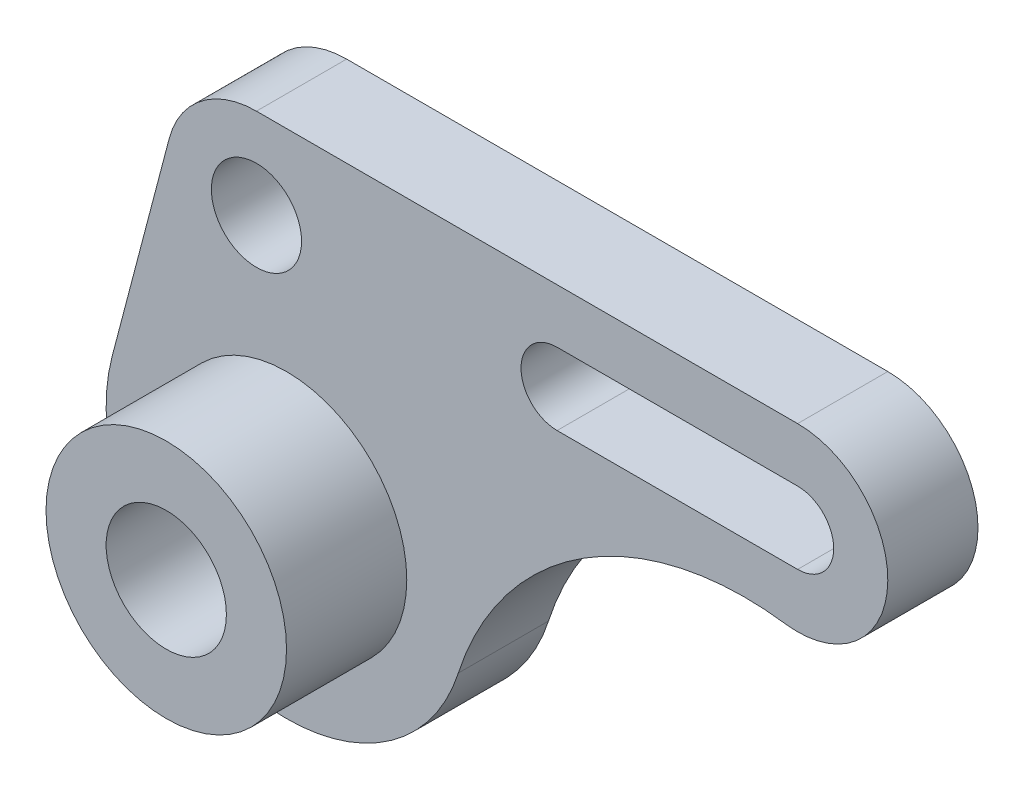
SolidWorks part; units mm, degrees
ref_plane "Front Plane" through (0, 0, 0) normal (0, 0, 1) x (1, 0, 0)
ref_plane "Top Plane" through (0, 0, 0) normal (0, 1, 0) x (1, 0, 0)
ref_plane "Right Plane" through (0, 0, 0) normal (1, 0, 0) x (0, 0, -1)
sketch "Sketch1" plane through (0, 0, 0) normal (0, 0, 1) x (1, 0, 0)
  line L0 (62.6542, 28.7091) -> (102.6542, 28.7091) construction
  line L1 (62.6542, 34.7091) -> (102.6542, 34.7091)
  line L2 (62.6542, 22.7091) -> (102.6542, 22.7091)
  line L3 (-11.3611, -3.6678) -> (-1.8534, 32.5207)
  line L4 (12.6542, 43.7091) -> (102.6542, 43.7091)
  circle A0 centre (12.6542, 28.7091) radius 7.5
  circle A1 centre (17.6542, -11.2909) radius 20
  circle A2 centre (17.6542, -11.2909) radius 10
  arc A4 (12.6542, 43.7091) -> (-1.8534, 32.5207) centre (12.6542, 28.7091) ccw
  arc A5 (62.6542, 34.7091) -> (62.6542, 22.7091) centre (62.6542, 28.7091) ccw
  arc A6 (102.6542, 22.7091) -> (102.6542, 34.7091) centre (102.6542, 28.7091) ccw
  arc A7 (100.6207, 13.8476) -> (102.6542, 43.7091) centre (102.6542, 28.7091) ccw
  arc A8 (46.2248, -20.4408) -> (100.6207, 13.8476) centre (93.8424, -35.6908) cw
  arc A9 (-11.3611, -3.6678) -> (46.2248, -20.4408) centre (17.6542, -11.2909) ccw
  point P9 (82.6542, 28.7091)
  point P23 (0, 0)
  dimension "D1" = 20
  dimension "D2" = 40
  dimension "D4" = 15
  dimension "D5" = 30
  dimension "D8" = 30
  dimension "D9" = 85
  dimension "D12" = 50
  dimension "D6" = 6
  dimension "D7" = 40
  dimension "D10" = 50
  dimension "D11" = 40
extrude "Boss-Extrude3" add sketch "Sketch1" along normal blind 15 contours A1 | A7 L4 A4 L3 A9 A8 | A0 | L2 A6 L1 A5
extrude "Boss-Extrude4" add sketch "Sketch1<9>" along normal blind 35 contours A2 | A1
sketch "Sketch1<9>" plane through (0, 0, 0) normal (0, 0, 1) x (1, 0, 0) same geometry as "Sketch1"
